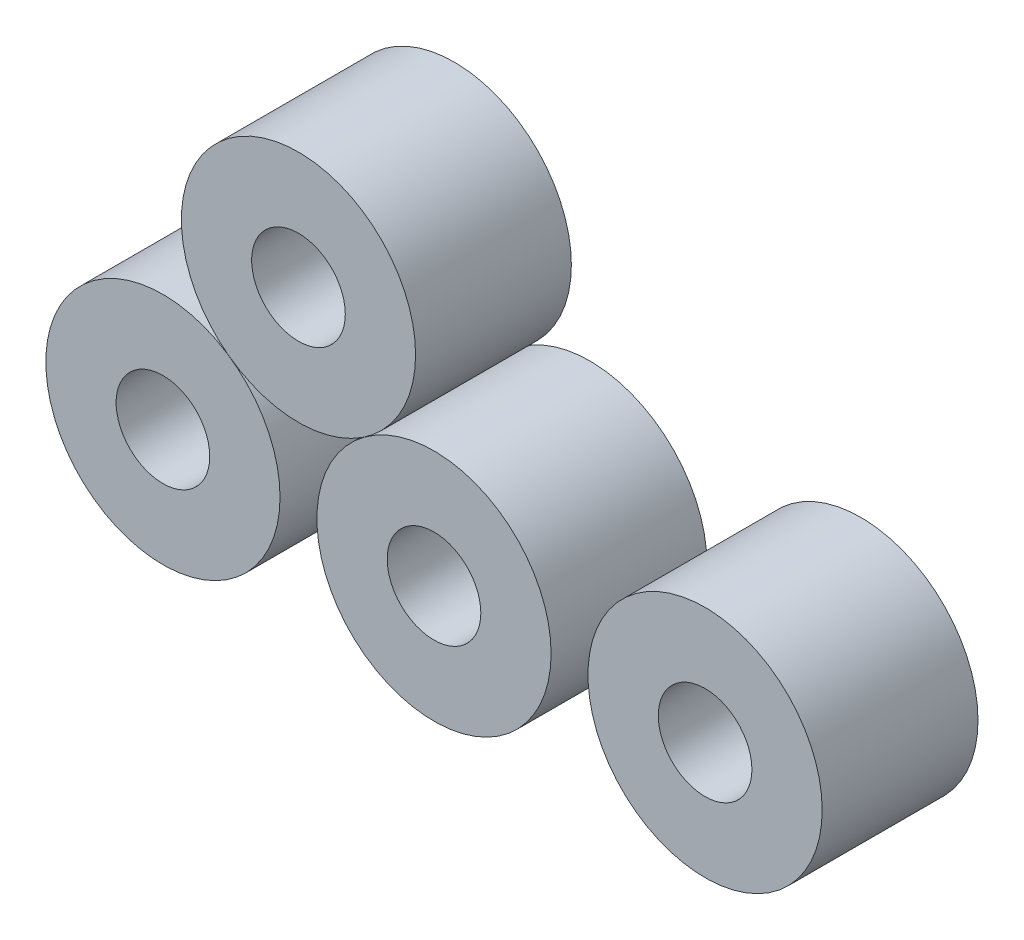
SolidWorks part; units mm, degrees
ref_plane "Płaszczyzna przednia" through (0, 0, 0) normal (0, 0, 1) x (1, 0, 0)
ref_plane "Płaszczyzna górna" through (0, 0, 0) normal (0, 1, 0) x (1, 0, 0)
ref_plane "Płaszczyzna prawa" through (0, 0, 0) normal (1, 0, 0) x (0, 0, -1)
sketch "Szkic1" plane through (0, 0, 0) normal (0, 0, 1) x (1, 0, 0)
  circle A0 centre (0, 0) radius 381
  circle A1 centre (0, 0) radius 953
  circle A2 centre (2206, 0) radius 953
  circle A3 centre (2206, 0) radius 381
  circle A4 centre (4412, 0) radius 953
  circle A5 centre (4412, 0) radius 381
  circle A10 centre (1103, 1554.4218) radius 953
  circle A11 centre (1103, 1554.4218) radius 381
  circle A12 centre (5515, 1554.4218) radius 381 [skipped]
  circle A13 centre (3309, 1554.4218) radius 953 [skipped]
  circle A14 centre (3309, 1554.4218) radius 381 [skipped]
  circle A15 centre (5515, 1554.4218) radius 953 [skipped]
  point P5 (0, 0)
  point P6 (0, 0)
  point P12 (0, 0)
  dimension "D1" = 762
  dimension "D2" = 1906
  dimension "D5" = 2206
  dimension "D3" = 3
  dimension "D4" = 2
extrude "Dodanie-wyciągnięcie1" add sketch "Szkic1" along normal blind 1268 contours A1 | A0 | A11 | A10 | A3 | A2 | A5 | A4
ref_axis "Oś1" through (0, 0, 1268) along (0, 0, -1)
ref_axis "Oś2" through (2206, 0, 1268) along (0, 0, -1)
ref_axis "Oś3" through (4412, 0, 1268) along (0, 0, -1)
ref_axis "Oś4" through (1103, 1554.4218, 1268) along (0, 0, -1)
